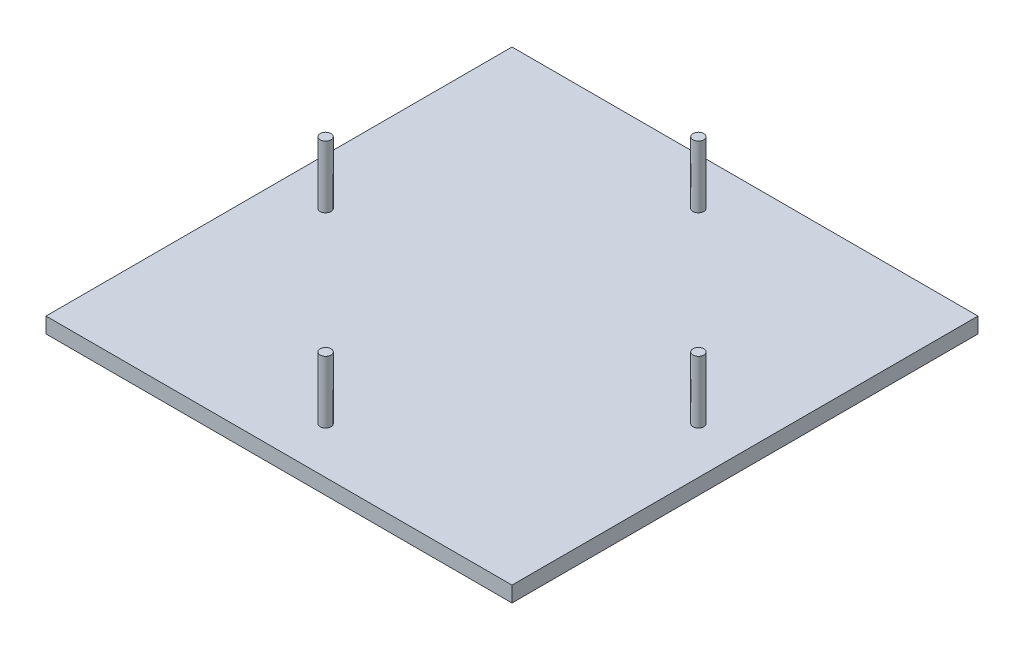
SolidWorks part; units mm, degrees
ref_plane "Front Plane" through (0, 0, 0) normal (0, 0, 1) x (1, 0, 0)
ref_plane "Top Plane" through (0, 0, 0) normal (0, 1, 0) x (1, 0, 0)
ref_plane "Right Plane" through (0, 0, 0) normal (1, 0, 0) x (0, 0, -1)
sketch "Sketch1" plane through (0, 0, 0) normal (0, 1, 0) x (1, 0, 0)
  line L1 (-75, 75) -> (75, 75)
  line L2 (-75, 75) -> (-75, -75)
  line L3 (-75, -75) -> (75, -75)
  line L4 (75, 75) -> (75, -75)
  line L5 (-75, 75) -> (75, -75) construction
  line L6 (-75, -75) -> (75, 75) construction
  point P0 (0, 0)
  dimension "D1" = 150
extrude "Boss-Extrude1" add sketch "Sketch1" along normal blind 5
sketch "Sketch2" plane through (0, 5, 0) normal (0, 1, 0) x (1, 0, 0)
  line L0 (-75, 0) -> (75, 0) construction
  line L1 (-75, 75) -> (-75, -75) construction
  line L2 (75, -75) -> (75, 75) construction
  line L3 (0, 0) -> (0, 18.8797) construction
  circle A0 centre (-60, 0) radius 1.75
  circle A2 centre (0, 60) radius 1.75
  circle A3 centre (60, 0) radius 1.75
  circle A4 centre (0, -60) radius 1.75
  point P6 (-60, 0)
  dimension "D2" = 3.5
  dimension "D3" = 4
  dimension "D1" = 15
extrude "Boss-Extrude2" add sketch "Sketch2" along normal blind 20
sketch "Sketch3" plane through (0, 0, 0) normal (0, -1, 0) x (1, 0, 0)
  line L1 (-75, 75) -> (75, 75)
  line L2 (-75, 75) -> (-75, -75)
  line L3 (-75, -75) -> (75, -75)
  line L4 (75, 75) -> (75, -75)
  line L9 (-15, 15) -> (15, -15) construction
  line L10 (-15, -15) -> (15, 15) construction
  circle A1 centre (0, 0) radius 15
  point P6 (0, 0)
  dimension "D1" = 30
  dimension "D2" = 30
extrude "Boss-Extrude4" add sketch "Sketch3" along normal blind 2 contours A1 region at (0, 0, 0)
sketch "Sketch5" plane through (0, -2, 0) normal (0, -1, 0) x (1, 0, 0)
  circle A0 centre (0, 0) radius 6
  dimension "D1" = 12
extrude "Boss-Extrude5" add sketch "Sketch5" along normal blind 10
sketch "Sketch6" plane through (0, -12, 0) normal (0, -1, 0) x (1, 0, 0)
  circle A0 centre (0, 0) radius 15
extrude "Boss-Extrude6" add sketch "Sketch6" along normal blind 3
